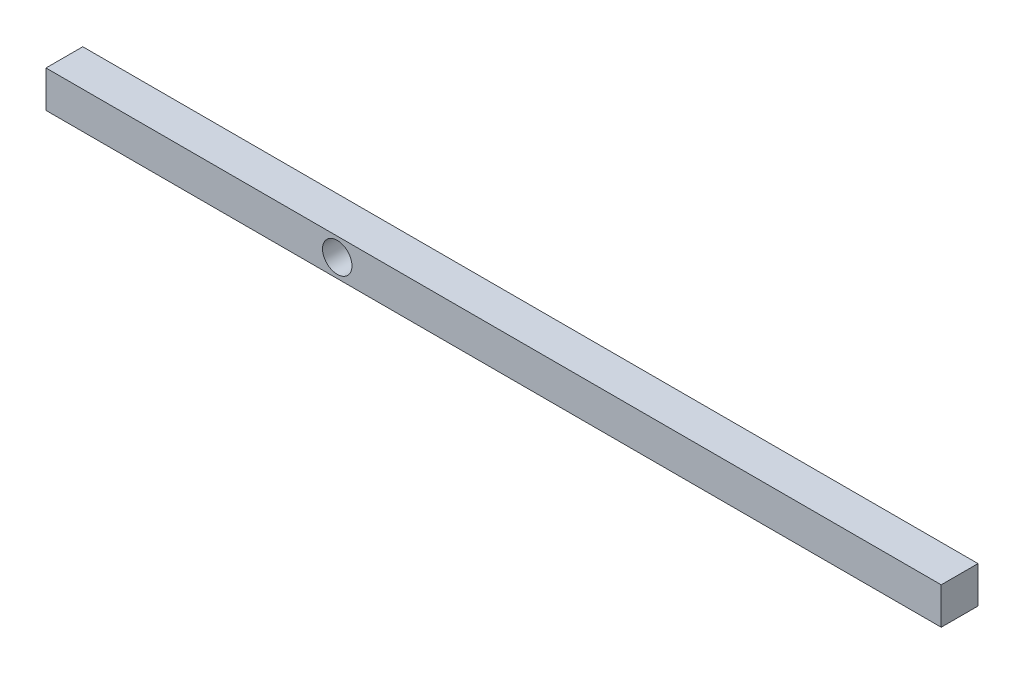
SolidWorks part; units mm, degrees
material "Plain Carbon Steel"
ref_plane "Front Plane" through (0, 0, 0) normal (0, 0, 1) x (1, 0, 0)
ref_plane "Top Plane" through (0, 0, 0) normal (0, 1, 0) x (1, 0, 0)
ref_plane "Right Plane" through (0, 0, 0) normal (1, 0, 0) x (0, 0, -1)
sketch "Sketch1" plane through (0, 0, 0) normal (0, 0, 1) x (1, 0, 0)
  line L0 (-95, -6) -> (197, -6)
  line L1 (197, -6) -> (197, 6)
  line L2 (197, 6) -> (-95, 6)
  line L3 (-95, 6) -> (-95, -6)
extrude "Boss-Extrude1" add sketch "Sketch1" along normal mid plane 12
sketch "Sketch2" plane through (0, 0, 0) normal (0, 0, 1) x (1, 0, 0)
  circle A0 centre (0, 0) radius 4.8
  dimension "D1" = 9.6
extrude "Cut-Extrude1" cut sketch "Sketch2" against normal mid plane 24
